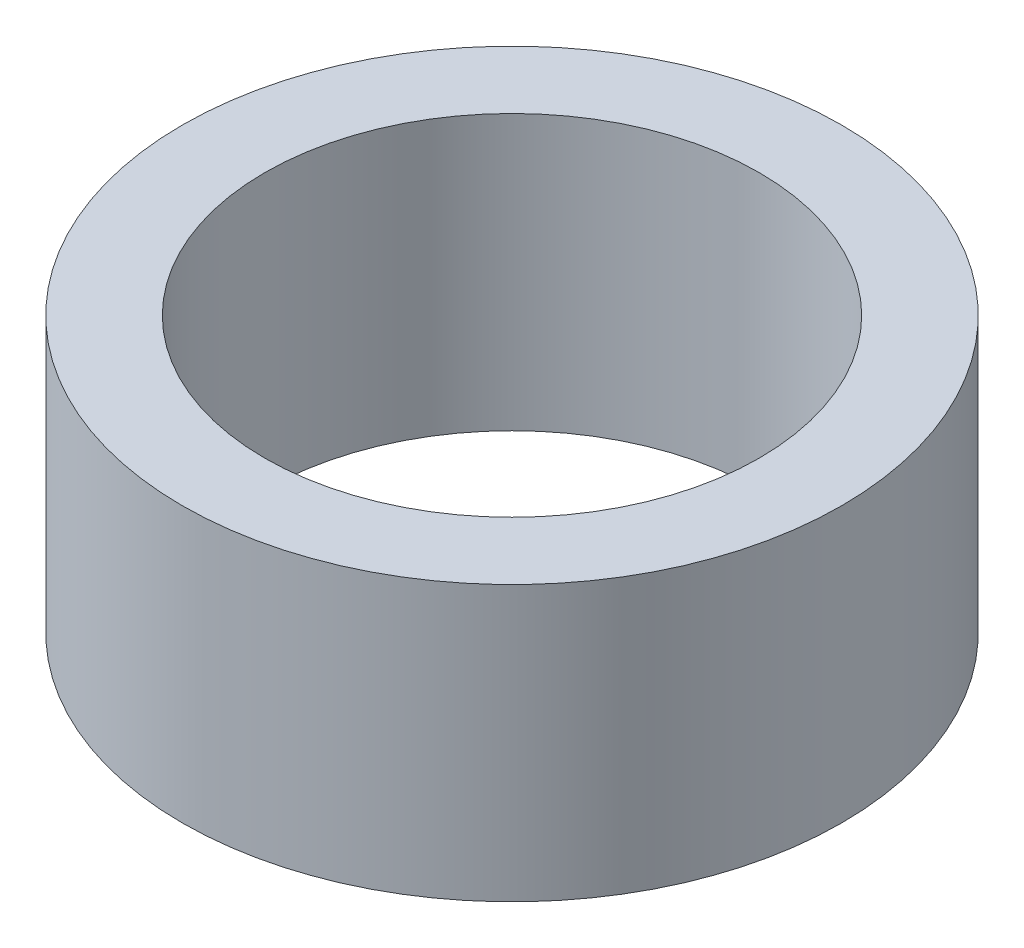
SolidWorks part; units mm, degrees
ref_plane "Plan de face" through (0, 0, 0) normal (0, 0, 1) x (1, 0, 0)
ref_plane "Plan de dessus" through (0, 0, 0) normal (0, 1, 0) x (1, 0, 0)
ref_plane "Plan de droite" through (0, 0, 0) normal (1, 0, 0) x (0, 0, -1)
sketch "Esquisse1" plane through (0, 0, 0) normal (0, 1, 0) x (1, 0, 0)
  circle A0 centre (0, 0) radius 2.25
  circle A1 centre (0, 0) radius 3
  dimension "D1" = 4.5
  dimension "D2" = 6
extrude "Boss.-Extru.1" add sketch "Esquisse1" along normal blind 2.5
